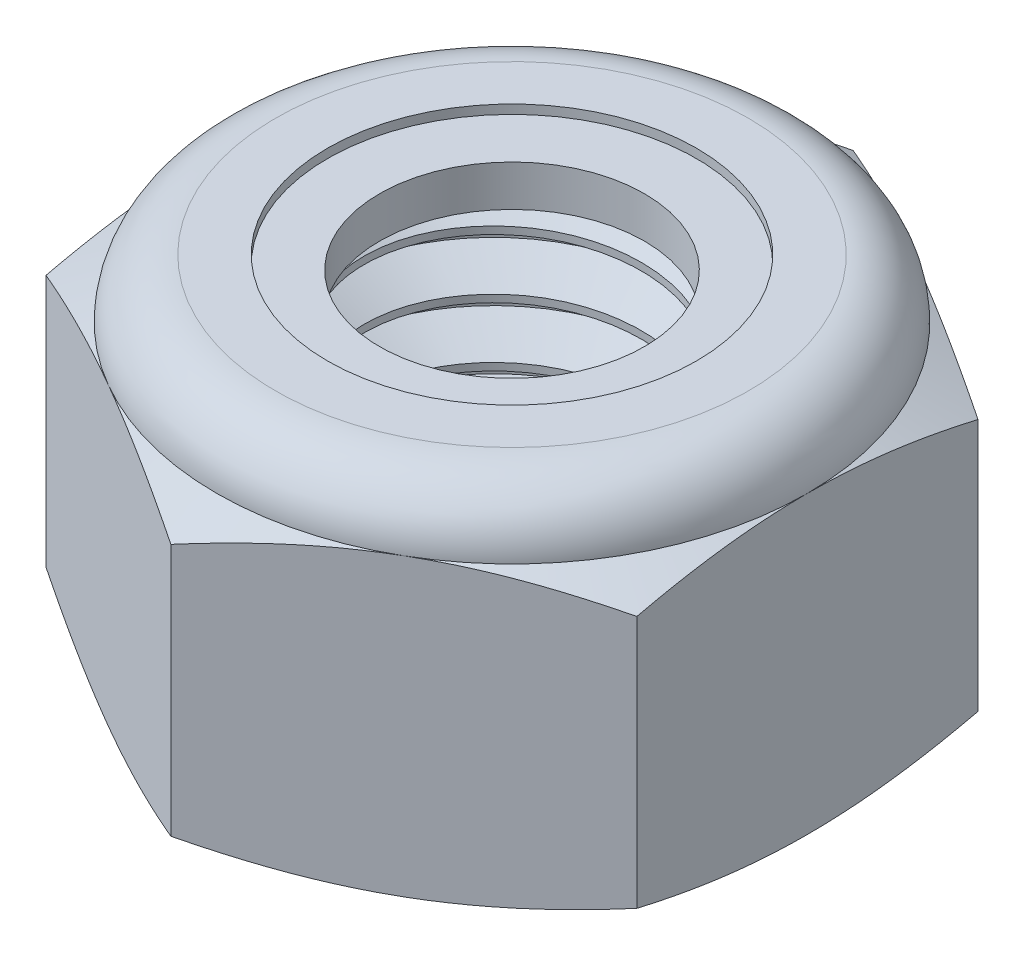
SolidWorks part; units mm, degrees
ref_plane "Front" through (0, 0, 0) normal (0, 0, 1) x (1, 0, 0)
ref_plane "Top" through (0, 0, 0) normal (0, 1, 0) x (1, 0, 0)
ref_plane "Right" through (0, 0, 0) normal (1, 0, 0) x (0, 0, -1)
sketch "Sketch1" plane through (0, 0, 0) normal (0, 1, 0) x (1, 0, 0)
  line L1 (0, 5.7735) -> (-5, 2.8868)
  line L2 (-5, 2.8868) -> (-5, -2.8868)
  line L3 (-5, -2.8868) -> (0, -5.7735)
  line L4 (0, -5.7735) -> (5, -2.8868)
  line L5 (5, -2.8868) -> (5, 2.8868)
  line L6 (5, 2.8868) -> (0, 5.7735)
  circle A0 centre (0, 0) radius 5 construction
  dimension "Hex Flats" = 10
extrude "Extrude1" add sketch "Sketch1" along normal blind 6
sketch "Sketch2" plane through (0, 0, 0) normal (1, 0, 0) x (0, 0, -1)
  line L0 (-3, 0) -> (-3, 6) construction
  line L1 (0, 0) -> (3, 0)
  line L2 (0, 0) -> (0, 6)
  line L3 (0, 6) -> (3, 6)
  line L4 (3, 0) -> (3, 6)
  line L5 (-2.8868, 6) -> (2.8868, 6) construction
  line L7 (0, -3) -> (0, 0) construction
  dimension "Thread Dia" = 6
revolve "Revolve1" add sketch "Sketch2" angle 360 about L7
sketch "Sketch8" plane through (0, 0, 0) normal (0, -1, 0) x (1, 0, 0)
  circle A1 centre (0, 0) radius 3
  circle A2 centre (0, 0) radius 3
  dimension "D1" = 0
curve "Helix/Spiral1" pitch 1 height 7 turns 7 parameters "Pitch"=1
sketch "Sketch10" plane through (0, 0, 0) normal (0, -1, 0) x (1, 0, 0)
  circle A1 centre (0, 0) radius 3
  circle A2 centre (0, 0) radius 3
  dimension "D1" = 0
extrude "Boss-Extrude1" add sketch "Sketch10" against normal through all draft 45
sketch "Sketch11" plane through (0, 6, 0) normal (0, 1, 0) x (1, 0, 0)
  circle A1 centre (0, 0) radius 3
  circle A2 centre (0, 0) radius 3
  dimension "D1" = 0
extrude "Boss-Extrude2" add sketch "Sketch11" against normal through all draft 45
sketch "Sketch9" plane through (0, 0, 0) normal (1, 0, 0) x (0, 0, -1)
  line L0 (3, -0.875) -> (3, 0)
  line L1 (3, -0.875) -> (2.3505, -0.5)
  line L2 (2.3505, -0.5) -> (2.3505, -0.375)
  line L3 (2.3505, -0.375) -> (3, 0)
  line L4 (-3, 0) -> (3, 0) construction
  line L5 (3, -0.4375) -> (2.3505, -0.4375) construction
  line L6 (2.6752, -0.6875) -> (2.6752, -0.1875) construction
  dimension "D1" = 0.125
  dimension "D2" = 0.5
  dimension "D3" = 60
sweep "Cut-Sweep1" cut profiles "Sketch9" path "Helix/Spiral1"
combine bodies "Combine1" operation type subtract main body 108 bodies to subtract 132
sketch "Sketch5" plane through (0, 0, 0) normal (1, 0, 0) x (0, 0, -1)
  line L0 (0, 0) -> (5, 0)
  line L1 (5, 0) -> (5.7735, 0.3607)
  line L2 (5.7735, 0.3607) -> (5.7735, 4.6393)
  line L3 (5.7735, 4.6393) -> (5, 5)
  line L4 (4, 6) -> (4, 7.27)
  line L5 (4, 7.27) -> (7.0435, 7.27)
  line L6 (7.0435, 7.27) -> (7.0435, -1.27)
  line L7 (7.0435, -1.27) -> (0, -1.27)
  line L8 (0, -1.27) -> (0, 0)
  line L9 (5, 5) -> (5, 0) construction
  line L10 (0, 0) -> (3, 0) construction
  line L13 (5.7735, 2.5) -> (7.0435, 2.5) construction
  line L14 (5.7735, 6) -> (5.7735, 0) construction
  line L15 (0, 0) -> (0, 7.27) construction
  line L20 (0, 7.27) -> (4, 7.27) construction
  line L22 (0, 6) -> (3, 6) construction
  arc A0 (5, 5) -> (4, 6) centre (4, 5) ccw
  dimension "D1" = 25
  dimension "D2" = 1.27
  dimension "D4" = 1
revolve "Cut-Revolve3" cut sketch "Sketch5" angle 360 about L15
sketch "Sketch6" plane through (0, 0, 0) normal (1, 0, 0) x (0, 0, -1)
  line L0 (0, 5) -> (4.8476, 5)
  line L1 (4, 5.8476) -> (3.1211, 5.8476)
  line L2 (0, 7.27) -> (0, 5)
  line L3 (3.1211, 7.27) -> (0, 7.27)
  line L4 (0, 7.27) -> (4, 7.27) construction
  line L5 (0, 0) -> (0, 7.27) construction
  line L6 (0, 7.27) -> (0, 0) construction
  line L7 (3.1211, 5.8476) -> (3.1211, 7.27)
  line L8 (4, 6) -> (4, 5.8476) construction
  line L9 (3.1211, 5.8476) -> (2.2422, 5.8476) construction
  line L10 (2.2422, 5.8476) -> (2.2422, 0) construction
  line L13 (2.2422, 5.4375) -> (3, 5) construction
  line L15 (3, 0) -> (3, 6) construction
  line L16 (2.2422, 5.5625) -> (3, 6) construction
  line L19 (2.6211, 5.2188) -> (2.6211, 5.7812) construction
  line L20 (2.2422, 5.4375) -> (2.2422, 5.5625) construction
  line L21 (3, 5) -> (3, 6) construction
  line L22 (3, 5.5) -> (2.2422, 5.5) construction
  arc A0 (4.8476, 5) -> (4, 5.8476) centre (4, 5) ccw
  arc A1 (5, 5) -> (4, 6) centre (4, 5) ccw construction
  dimension "D1" = 0.1524
  dimension "D2" = 1
  dimension "D3" = 0.125
  dimension "D4" = 60
revolve "Cut-Revolve4" cut sketch "Sketch6" angle 360 about L6
sketch "Sketch7" plane through (0, 0, 0) normal (1, 0, 0) x (0, 0, -1)
  line L0 (2.2422, 5.0762) -> (4.7676, 5.0762)
  line L1 (4, 5.7714) -> (2.2422, 5.7714)
  line L2 (2.2422, 5.7714) -> (2.2422, 5.0762)
  line L3 (2.2422, 5.0762) -> (0, 5.0762) construction
  line L4 (0, 5.0762) -> (0, 5.7714) construction
  line L5 (0, 5.7714) -> (2.2422, 5.7714) construction
  line L6 (2.2422, 5.0762) -> (2.2422, 5) construction
  line L7 (0, 5) -> (4.8476, 5) construction
  line L8 (4, 5.7714) -> (4, 5.8476) construction
  line L9 (2.2422, 5.8476) -> (2.2422, 0) construction
  arc A0 (4.7676, 5.0762) -> (4, 5.7714) centre (4, 5) ccw
  arc A2 (4.8476, 5) -> (4, 5.8476) centre (4, 5) ccw construction
  dimension "D1" = 0.0762
revolve "Revolve2" add sketch "Sketch7" angle 360 about L4
move or copy body "Body-Move/Copy1" [suppressed] bodies to move or copy 115 116
equation "\"D4@Sketch5\"=\"Height@Extrude1\"/6"
equation "\"D3@Helix/Spiral1\"=\"Pitch@Helix/Spiral1\"+\"Height@Extrude1\""
equation "\"D1@Sketch9\"=\"Pitch@Helix/Spiral1\"*.125"
equation "\"D2@Sketch9\"=\"Pitch@Helix/Spiral1\"*.50"
equation "\"D2@Sketch6\"=\"Pitch@Helix/Spiral1\""
equation "\"D3@Sketch6\"=\"Pitch@Helix/Spiral1\"/8"
